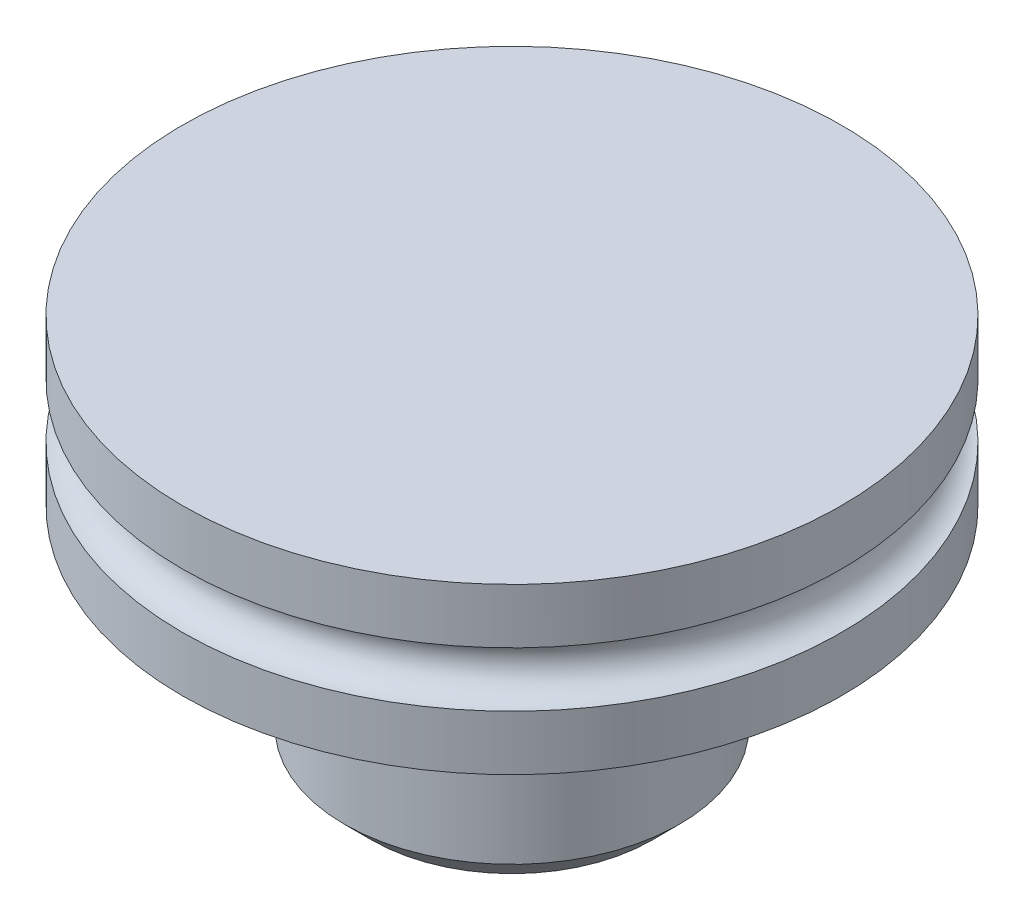
SolidWorks part; units mm, degrees
ref_plane "Front Plane" through (0, 0, 0) normal (0, 0, 1) x (1, 0, 0)
ref_plane "Top Plane" through (0, 0, 0) normal (0, 1, 0) x (1, 0, 0)
ref_plane "Right Plane" through (0, 0, 0) normal (1, 0, 0) x (0, 0, -1)
sketch "Sketch1" plane through (0, 0, 0) normal (0, 1, 0) x (1, 0, 0)
  circle A0 centre (0, 0) radius 3.05
  dimension "D1" = 6.1
extrude "Boss-Extrude1" add sketch "Sketch1" along normal blind 3
sketch "Sketch4" plane through (0, 3, 0) normal (0, 1, 0) x (1, 0, 0)
  circle A0 centre (0, 0) radius 3.6
  dimension "D1" = 7.2
extrude "Boss-Extrude3" add sketch "Sketch4" along normal blind 1
sketch "Sketch2" plane through (0, 4, 0) normal (0, 1, 0) x (1, 0, 0)
  circle A0 centre (0, 0) radius 6
  dimension "D1" = 12
extrude "Boss-Extrude2" add sketch "Sketch2" along normal blind 3
ref_axis "Axis1" through (0, 9.1152, 0) along (0, -1, 0)
sketch "Sketch3" plane through (0, 0, 0) normal (0, 0, 1) x (1, 0, 0)
  line L0 (-6, 7) -> (-6, 4) construction
  circle A0 centre (-6, 5.5) radius 0.5
  dimension "D1" = 1
revolve "Cut-Revolve1" cut sketch "Sketch3" angle 360 about axis through (0, 9.1152, 0) along (0, -1, 0)
chamfer "Chamfer1" distance 0.5 angle 45 1 edges at (0, 0, 3.05)
